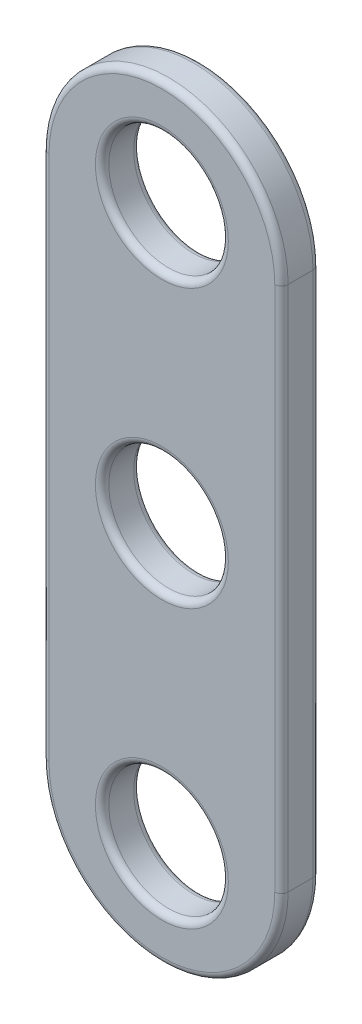
SolidWorks part; units mm, degrees
material "ABS"
ref_plane "Front Plane" through (0, 0, 0) normal (0, 0, 1) x (1, 0, 0)
ref_plane "Top Plane" through (0, 0, 0) normal (0, 1, 0) x (1, 0, 0)
ref_plane "Right Plane" through (0, 0, 0) normal (1, 0, 0) x (0, 0, -1)
sketch "Sketch1" plane through (0, 0, 0) normal (0, 0, 1) x (1, 0, 0)
  line L0 (0, 36.83) -> (0, -36.83) construction
  line L1 (-15.875, 50.8) -> (15.875, 50.8)
  line L2 (-15.875, 50.8) -> (-15.875, -50.8)
  line L3 (-15.875, -50.8) -> (15.875, -50.8)
  line L4 (15.875, 50.8) -> (15.875, -50.8)
  line L5 (-15.875, 50.8) -> (15.875, -50.8) construction
  line L6 (-15.875, -50.8) -> (15.875, 50.8) construction
  circle A0 centre (0, -36.83) radius 7.9375
  circle A2 centre (0, 0) radius 7.9375
  circle A3 centre (0, 36.83) radius 7.9375
  point P0 (0, 0)
  point P9 (0, 0)
  dimension "D4" = 15.875
  dimension "D1" = 31.75
  dimension "D2" = 101.6
  dimension "D3" = 36.83
extrude "Boss-Extrude1" add sketch "Sketch1" along normal blind 5.08
fillet "Fillet1" 2 edges at (15.875, 50.8, 2.54) (-15.875, 50.8, 2.54) type full round first side face at (15.875, 0, 2.54) second side face at (-15.875, 0, 2.54) middle face at (0, 50.8, 2.54)
fillet "Fillet2" 2 edges at (-15.875, -50.8, 2.54) (15.875, -50.8, 2.54) type full round first side face at (-15.875, -7.9375, 2.54) second side face at (15.875, -7.9375, 2.54) middle face at (0, -50.8, 2.54)
fillet "Fillet3" radius 0.889 14 edges at (7.9375, 36.83, 0) (7.9375, 0, 0) (7.9375, -36.83, 0) (0, 50.8, 0) (-15.875, 0, 0) (0, -50.8, 0) (15.875, 0, 0) (7.9375, 36.83, 5.08) (7.9375, -36.83, 5.08) (0, 50.8, 5.08) (15.875, 0, 5.08) (0, -50.8, 5.08) (-15.875, 0, 5.08) (7.9375, 0, 5.08)
